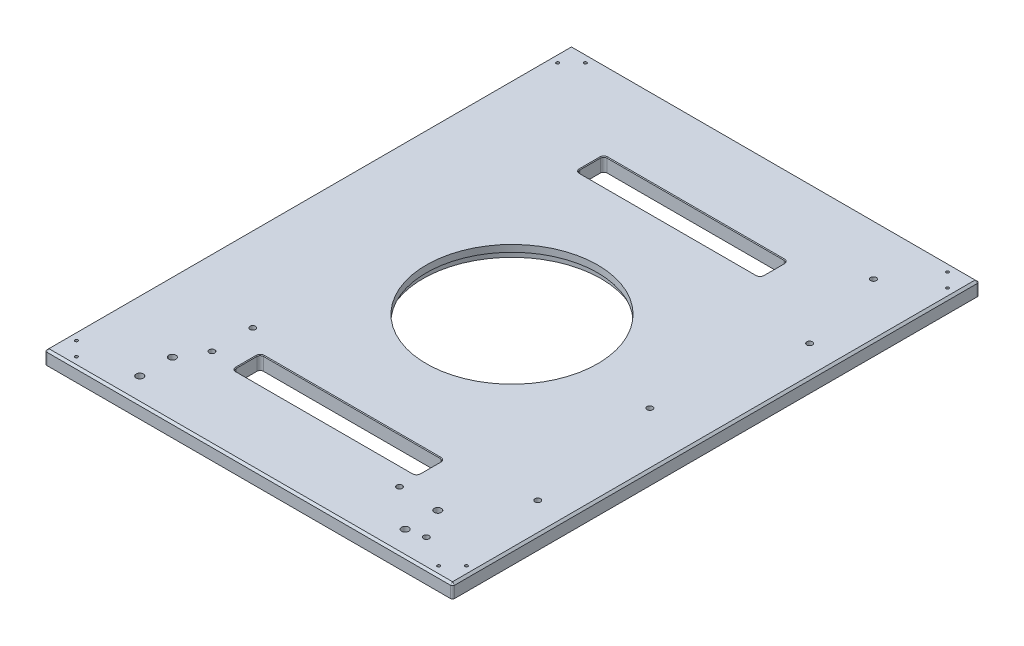
SolidWorks part; units mm, degrees
material "6061-T6 (SS)"
ref_plane "Front Plane" through (0, 0, 0) normal (0, 0, 1) x (1, 0, 0)
ref_plane "Top Plane" through (0, 0, 0) normal (0, 1, 0) x (1, 0, 0)
ref_plane "Right Plane" through (0, 0, 0) normal (1, 0, 0) x (0, 0, -1)
sketch "Sketch1" plane through (0, 0, 0) normal (0, 1, 0) x (1, 0, 0)
  line L1 (-300, -387.5) -> (300, -387.5)
  line L2 (-300, -387.5) -> (-300, 387.5)
  line L3 (-300, 387.5) -> (300, 387.5)
  line L4 (300, -387.5) -> (300, 387.5)
  line L5 (-300, -387.5) -> (300, 387.5) construction
  line L6 (-300, 387.5) -> (300, -387.5) construction
  point P0 (0, 0)
  dimension "D1" = 775
  dimension "D2" = 600
extrude "MainPlate" add sketch "Sketch1" against normal blind 20
sketch "Sketch2" plane through (0, -20, 0) normal (0, -1, 0) x (-1, 0, 0)
  circle A0 centre (0, 0) radius 126
  dimension "D1" = 252
extrude "BuildPlate" cut sketch "Sketch2" against normal through all
sketch "Sketch3" plane through (0, -20, 0) normal (0, 1, 0) x (-1, 0, 0)
  circle A0 centre (0, 0) radius 131
  dimension "D1" = 262
extrude "BuildCylinderRelief" cut sketch "Sketch3" along normal blind 10
hole_wizard "Z-axisHelicoils" positions "Sketch4" profile "Sketch5" tap size "M8x1.25" standard "Helicoil® Metric"
sketch "Sketch4" plane through (0, -20, 0) normal (0, 1, 0) x (1, 0, 0)
  line L0 (0, 0) -> (148.5, 0) construction
  circle A0 centre (0, 0) radius 148.5 construction
  point P0 (148.5, 0)
  dimension "D1" = 297
cosmetic thread "Hole Thread1" parameters "D1"=14.19, "D2"=9.787
sketch "Sketch5" plane through (148.5, -20, 0) normal (1, 0, 0) x (0, 0, -1)
  line L0 (0, 0) -> (0, 19.6436)
  line L1 (0, 19.6436) -> (4.15, 17.15)
  line L2 (4.15, 17.15) -> (4.15, 0)
  line L5 (4.15, 0) -> (0, 0)
  line L10 (0, 19.6436) -> (-4.15, 17.15) construction
  line L11 (0, -6.35) -> (0, 107.95) construction
  dimension "Tap Drill Dia." = 8.3
  dimension "Tap Drill Depth" = 17.15
  dimension "Drill Angle" = 118
pattern_circular "Z-axisMountHoles" count 6 over 360 about axis through (0, -10, 0) along (0, -1, 0) of "Z-axisHelicoils"
cosmetic thread "Hole Thread2" parameters "D1"=14.19, "D2"=9.787
cosmetic thread "Hole Thread3" parameters "D1"=14.19, "D2"=9.787
cosmetic thread "Hole Thread4" parameters "D1"=14.19, "D2"=9.787
cosmetic thread "Hole Thread5" parameters "D1"=14.19, "D2"=9.787
cosmetic thread "Hole Thread6" parameters "D1"=14.19, "D2"=9.787
sketch "Sketch6" plane through (0, -20, 0) normal (0, -1, 0) x (-1, 0, 0)
  line L0 (0, 0) -> (0, 250) construction
  line L1 (130, 230) -> (-130, 230)
  line L2 (135, 235) -> (135, 265)
  line L3 (130, 270) -> (-130, 270)
  line L4 (-135, 235) -> (-135, 265)
  line L5 (135, 230) -> (-135, 270) construction
  line L6 (135, 270) -> (-135, 230) construction
  arc A0 (135, 265) -> (130, 270) centre (130, 265) ccw
  arc A1 (130, 230) -> (135, 235) centre (130, 235) ccw
  arc A2 (-130, 230) -> (-135, 235) centre (-130, 235) cw
  arc A3 (-130, 270) -> (-135, 265) centre (-130, 265) ccw
  point P0 (0, 250)
  dimension "D4" = 5
  dimension "D1" = 230
  dimension "D2" = 40
  dimension "D3" = 270
extrude "Overflow" cut sketch "Sketch6" against normal through all
hole_wizard "M5 Tapped Hole1" positions "Sketch7" profile "Sketch8" tap size "M5" standard "ISO"
sketch "Sketch7" plane through (0, -20, 0) normal (0, 1, 0) x (1, 0, 0)
  line L0 (130, 230) -> (-130, 230) construction
  line L1 (0, 217) -> (0, 0) construction
  line L3 (135, 250) -> (-135, 250) construction
  line L4 (135, 265) -> (135, 235) construction
  line L5 (-135, 235) -> (-135, 265) construction
  line L7 (148, 250) -> (135, 250) construction
  line L9 (0, 217) -> (60, 217) construction
  line L10 (60, 217) -> (120, 217) construction
  line L12 (148, 217) -> (148, 250) construction
  line L15 (148, 217) -> (120, 217) construction
  point P0 (0, 217)
  point P8 (120, 217)
  point P10 (60, 217)
  point P12 (148, 250)
  point P38 (148, 217)
  dimension "D1" = 13
  dimension "D2" = 13
  dimension "D3" = 60
sketch "Sketch8" plane through (0, -20, -217) normal (1, 0, 0) x (0, 0, -1)
  line L0 (0, 0) -> (0, 13.6618)
  line L1 (0, 13.6618) -> (2.1, 12.4)
  line L2 (2.1, 12.4) -> (2.1, 0)
  line L5 (2.1, 0) -> (0, 0)
  line L10 (0, 13.6618) -> (-2.1, 12.4) construction
  line L11 (0, -6.35) -> (0, 107.95) construction
  dimension "Tap Drill Dia." = 4.2
  dimension "Tap Drill Depth" = 12.4
  dimension "Drill Angle" = 118
cosmetic thread "Hole Thread7" parameters "D1"=10, "D2"=5
cosmetic thread "Hole Thread32" parameters "D1"=10, "D2"=5
cosmetic thread "Hole Thread33" parameters "D1"=10, "D2"=5
cosmetic thread "Hole Thread34" parameters "D1"=10, "D2"=5
cosmetic thread "Hole Thread96" parameters "D1"=10, "D2"=5
mirror "Mirror3" about plane through (0, 0, 0) normal (1, 0, 0) of "M5 Tapped Hole1"
cosmetic thread "Hole Thread35" parameters "D1"=10, "D2"=5
cosmetic thread "Hole Thread36" parameters "D1"=10, "D2"=5
cosmetic thread "Hole Thread37" parameters "D1"=10, "D2"=5
cosmetic thread "Hole Thread97" parameters "D1"=10, "D2"=5
ref_plane "Plane1" through (0, 0, -250) normal (0, 0, 1) x (1, 0, 0)
mirror "Mirror4" about plane through (0, 0, -250) normal (0, 0, 1) of "Mirror3"
cosmetic thread "Hole Thread39" parameters "D1"=10, "D2"=5
cosmetic thread "Hole Thread40" parameters "D1"=10, "D2"=5
cosmetic thread "Hole Thread42" parameters "D1"=10, "D2"=5
cosmetic thread "Hole Thread44" parameters "D1"=10, "D2"=5
cosmetic thread "Hole Thread98" parameters "D1"=10, "D2"=5
cosmetic thread "Hole Thread99" parameters "D1"=10, "D2"=5
sketch "Sketch9" plane through (0, 0, 0) normal (0, 1, 0) x (-1, 0, 0)
  line L4 (-130, -270) -> (130, -270)
  line L5 (-135, -235) -> (-135, -265)
  line L6 (130, -230) -> (-130, -230)
  line L7 (135, -265) -> (135, -235)
  line L8 (-130, -270) -> (130, -270) construction
  line L9 (-135, -235) -> (-135, -265) construction
  line L10 (130, -230) -> (-130, -230) construction
  line L11 (135, -265) -> (135, -235) construction
  arc A4 (130, -270) -> (135, -265) centre (130, -265) ccw
  arc A5 (-135, -265) -> (-130, -270) centre (-130, -265) ccw
  arc A6 (-130, -230) -> (-135, -235) centre (-130, -235) ccw
  arc A7 (135, -235) -> (130, -230) centre (130, -235) ccw
  arc A8 (130, -270) -> (135, -265) centre (130, -265) ccw construction
  arc A9 (-135, -265) -> (-130, -270) centre (-130, -265) ccw construction
  arc A10 (-130, -230) -> (-135, -235) centre (-130, -235) ccw construction
  arc A11 (135, -235) -> (130, -230) centre (130, -235) ccw construction
  spline S0 degree 3 poles (135, -263.0491) (135, -254.3497) (135, -245.6503) (135, -236.9509) (135, -236.7341) (135, -236.3006) (135, -235.6503) (135, -235.2168) (135, -235) (135, -234.7832) (135, -234.3497) (134.8422, -233.6982) (134.7024, -233.2868) (134.6194, -233.0866) (134.1051, -231.8451) (133.1549, -230.8949) (131.9134, -230.3806) (131.7132, -230.2976) (131.3018, -230.1578) (130.6503, -230) (130.2168, -230) (130, -230) (129.7832, -230) (129.3497, -230) (128.6994, -230) (128.2659, -230) (128.0491, -230) (42.683, -230) (-42.683, -230) (-128.0491, -230) (-128.2659, -230) (-128.6994, -230) (-129.3497, -230) (-129.7832, -230) (-130, -230) (-130.2168, -230) (-130.6503, -230) (-131.3018, -230.1578) (-131.7132, -230.2976) (-131.9134, -230.3806) (-133.1549, -230.8949) (-134.1051, -231.8451) (-134.6194, -233.0866) (-134.7024, -233.2868) (-134.8422, -233.6982) (-135, -234.3497) (-135, -234.7832) (-135, -235) (-135, -235.2168) (-135, -235.6503) (-135, -236.3006) (-135, -236.7341) (-135, -236.9509) (-135, -245.6503) (-135, -254.3497) (-135, -263.0491) (-135, -263.2659) (-135, -263.6994) (-135, -264.3497) (-135, -264.7832) (-135, -265) (-135, -265.2168) (-135, -265.6503) (-134.8422, -266.3018) (-134.7024, -266.7132) (-134.6194, -266.9134) (-134.1051, -268.1549) (-133.1549, -269.1051) (-131.9134, -269.6194) (-131.7132, -269.7024) (-131.3018, -269.8422) (-130.6503, -270) (-130.2168, -270) (-130, -270) (-129.7832, -270) (-129.3497, -270) (-128.6994, -270) (-128.2659, -270) (-128.0491, -270) (-42.683, -270) (42.683, -270) (128.0491, -270) (128.2659, -270) (128.6994, -270) (129.3497, -270) (129.7832, -270) (130, -270) (130.2168, -270) (130.6503, -270) (131.3018, -269.8422) (131.7132, -269.7024) (131.9134, -269.6194) (133.1549, -269.1051) (134.1051, -268.1549) (134.6194, -266.9134) (134.7024, -266.7132) (134.8422, -266.3018) (135, -265.6503) (135, -265.2168) (135, -265) (135, -264.7832) (135, -264.3497) (135, -263.6994) (135, -263.2659) (135, -263.0491) (135, -254.3497) (135, -245.6503) knots -0.001064 0 0 0 0.04272 0.04272 0.04272 0.043784 0.044849 0.045913 0.045913 0.045913 0.046978 0.048042 0.049107 0.049107 0.049107 0.055371 0.055371 0.055371 0.056435 0.0575 0.058564 0.058564 0.058564 0.059629 0.060693 0.061758 0.061758 0.061758 0.480962 0.480962 0.480962 0.482027 0.483091 0.484156 0.484156 0.484156 0.48522 0.486285 0.487349 0.487349 0.487349 0.493613 0.493613 0.493613 0.494678 0.495742 0.496807 0.496807 0.496807 0.497871 0.498936 0.5 0.5 0.5 0.54272 0.54272 0.54272 0.543784 0.544849 0.545913 0.545913 0.545913 0.546978 0.548042 0.549107 0.549107 0.549107 0.555371 0.555371 0.555371 0.556435 0.5575 0.558564 0.558564 0.558564 0.559629 0.560693 0.561758 0.561758 0.561758 0.980962 0.980962 0.980962 0.982027 0.983091 0.984156 0.984156 0.984156 0.98522 0.986285 0.987349 0.987349 0.987349 0.993613 0.993613 0.993613 0.994678 0.995742 0.996807 0.996807 0.996807 0.997871 0.998936 1 1 1 1.04272 1.04272 1.04272 weights 1 1 1 1 1 1 1 1 1 1 1 1 1 1 0.949253 0.949253 1 1 1 1 1 1 1 1 1 1 1 1 1 1 1 1 1 1 1 1 1 1 1 1 0.949253 0.949253 1 1 1 1 1 1 1 1 1 1 1 1 1 1 1 1 1 1 1 1 1 1 1 1 0.949253 0.949253 1 1 1 1 1 1 1 1 1 1 1 1 1 1 1 1 1 1 1 1 1 1 1 1 0.949253 0.949253 1 1 1 1 1 1 1 1 1 1 1 1 1 only from (135, -263.0491) to (135, -263.0491)
  dimension "D1" = 0
sketch "Sketch10" plane through (0, 0, 0) normal (0, 1, 0) x (1, 0, 0)
  line L0 (0, 0) -> (0, -255.5) construction
  line L1 (-130, -275.5) -> (130, -275.5)
  line L2 (-135, -270.5) -> (-135, -240.5)
  line L3 (-130, -235.5) -> (130, -235.5)
  line L4 (135, -270.5) -> (135, -240.5)
  line L5 (-135, -275.5) -> (135, -235.5) construction
  line L6 (-135, -235.5) -> (135, -275.5) construction
  line L7 (-300, -387.5) -> (300, -387.5) construction
  line L8 (0, 230) -> (0, 270) construction
  line L9 (-130, 230) -> (130, 230) construction
  line L10 (-130, 270) -> (130, 270) construction
  line L11 (0, -275.5) -> (0, -235.5) construction
  arc A0 (130, -275.5) -> (135, -270.5) centre (130, -270.5) ccw
  arc A1 (130, -235.5) -> (135, -240.5) centre (130, -240.5) cw
  arc A2 (-130, -275.5) -> (-135, -270.5) centre (-130, -270.5) cw
  arc A3 (-135, -240.5) -> (-130, -235.5) centre (-130, -240.5) cw
  point P0 (0, -255.5)
  dimension "D4" = 5
  dimension "D1" = 270
  dimension "D3" = 132
extrude "Cut-Extrude1" cut sketch "Sketch10" against normal through all
sketch "Sketch11" plane through (0, 0, 0) normal (0, 1, 0) x (1, 0, 0)
  line L1 (300, 387.5) -> (280, 387.5) construction
  line L2 (300, 387.5) -> (300, 367.5) construction
  line L3 (300, 367.5) -> (280, 367.5) construction
  line L4 (280, 387.5) -> (280, 367.5) construction
  dimension "D1" = 20
sketch "Sketch12" plane through (0, -20, 0) normal (0, -1, 0) x (-1, 0, 0)
  line L0 (-300, -387.5) -> (-300, 387.5) construction
  line L1 (-240, -327.5) -> (240, -327.5) construction
  line L2 (-240, -327.5) -> (-240, 327.5) construction
  line L3 (-240, 327.5) -> (240, 327.5) construction
  line L4 (240, -327.5) -> (240, 327.5) construction
  line L5 (300, -387.5) -> (-300, -387.5) construction
  line L6 (0, 0) -> (0, -327.5) construction
  line L7 (-240, 0) -> (0, 0) construction
  dimension "D1" = 60
  dimension "D2" = 60
hole_wizard "M8 Tapped Hole1" positions "Sketch13" profile "Sketch14" tap size "M8" standard "ISO"
sketch "Sketch13" plane through (0, -20, 0) normal (0, -1, 0) x (-1, 0, 0)
  line L0 (-240, -327.5) -> (-240, 327.5) construction
  line L1 (-240, 327.5) -> (240, 327.5) construction
  line L2 (-240, 0) -> (0, 0) construction
  line L3 (0, 0) -> (0, -327.5) construction
  line L4 (0, 0) -> (0, -327.5) construction
  line L5 (-240, 0) -> (0, 0) construction
  point P0 (-240, 150)
  point P4 (-110, 327.5)
  point P14 (-240, -150)
  point P15 (-110, -327.5)
  point P16 (110, -327.5)
  point P17 (240, -150)
  point P18 (240, 150)
  point P19 (110, 327.5)
  dimension "D1" = 150
  dimension "D2" = 130
sketch "Sketch14" plane through (240, -20, -150) normal (1, 0, 0) x (0, 0, -1)
  line L0 (0, 0) -> (0, 15)
  line L1 (0, 15) -> (3.4, 12.9571)
  line L2 (3.4, 12.9571) -> (3.4, 0)
  line L5 (3.4, 0) -> (0, 0)
  line L10 (0, 15) -> (-3.4, 12.9571) construction
  line L11 (0, -6.35) -> (0, 107.95) construction
  dimension "Tap Drill Dia." = 6.8
  dimension "Tap Drill Depth" = 15
  dimension "Drill Angle" = 118
cosmetic thread "Hole Thread15" parameters "D1"=12, "D2"=8
cosmetic thread "Hole Thread16" parameters "D1"=12, "D2"=8
cosmetic thread "Hole Thread17" parameters "D1"=12, "D2"=8
cosmetic thread "Hole Thread18" parameters "D1"=12, "D2"=8
cosmetic thread "Hole Thread19" parameters "D1"=12, "D2"=8
cosmetic thread "Hole Thread20" parameters "D1"=12, "D2"=8
cosmetic thread "Hole Thread21" parameters "D1"=12, "D2"=8
cosmetic thread "Hole Thread22" parameters "D1"=12, "D2"=8
hole_wizard "M5 Tapped Hole2" positions "Sketch15" profile "Sketch16" tap size "M5" standard "ISO"
sketch "Sketch15" plane through (0, 0, 0) normal (0, 1, 0) x (1, 0, 0)
  line L0 (300, 387.5) -> (-300, 387.5) construction
  line L1 (300, -387.5) -> (300, 387.5) construction
  point P0 (266.5, 374.5)
  point P2 (287, 354)
  dimension "D1" = 13
  dimension "D2" = 33.5
  dimension "D3" = 13
  dimension "D4" = 33.5
sketch "Sketch16" plane through (266.5, 0, -374.5) normal (1, 0, 0) x (0, 0, 1)
  line L0 (0, 0) -> (0, 12.4)
  line L1 (0, 12.4) -> (2.1, 11.1382)
  line L2 (2.1, 11.1382) -> (2.1, 0)
  line L5 (2.1, 0) -> (0, 0)
  line L10 (0, 12.4) -> (-2.1, 11.1382) construction
  line L11 (0, -6.35) -> (0, 107.95) construction
  dimension "Tap Drill Dia." = 4.2
  dimension "Tap Drill Depth" = 12.4
  dimension "Drill Angle" = 118
cosmetic thread "Hole Thread23" parameters "D1"=10, "D2"=5
cosmetic thread "Hole Thread24" parameters "D1"=10, "D2"=5
mirror "Mirror1" about plane through (0, 0, 0) normal (1, 0, 0) of "M5 Tapped Hole2"
cosmetic thread "Hole Thread25" parameters "D1"=10, "D2"=5
cosmetic thread "Hole Thread26" parameters "D1"=10, "D2"=5
mirror "Mirror2" about plane through (0, 0, 0) normal (0, 0, 1) of "Mirror1"
cosmetic thread "Hole Thread27" parameters "D1"=10, "D2"=5
cosmetic thread "Hole Thread28" parameters "D1"=10, "D2"=5
cosmetic thread "Hole Thread29" parameters "D1"=10, "D2"=5
cosmetic thread "Hole Thread30" parameters "D1"=10, "D2"=5
chamfer "Chamfer1" distance 1 angle 45 16 edges at (0, 0, -270) (133.5355, 0, -268.5355) (-133.5355, 0, -268.5355) (135, 0, -250) (-135, 0, -250) (133.5355, 0, -231.4645) (-133.5355, 0, -231.4645) (0, 0, -230) (133.5355, 0, 274.0355) (135, 0, 255.5) (133.5355, 0, 236.9645) (0, 0, 235.5) (-133.5355, 0, 236.9645) (-135, 0, 255.5) (-133.5355, 0, 274.0355) (0, 0, 275.5)
fillet "Fillet1" radius 3 4 edges at (-300, -10, -387.5) (-300, -10, 387.5) (300, -10, 387.5) (300, -10, -387.5)
chamfer "Chamfer2" distance 3 angle 45 8 edges at (0, 0, 387.5) (-300, 0, 0) (0, 0, -387.5) (300, 0, 0) (299.1213, 0, -386.6213) (299.1213, 0, 386.6213) (-299.1213, 0, 386.6213) (-299.1213, 0, -386.6213)
pattern_linear "LPattern1" count 2 spacing 505.5 along (0, 0, 1) of "Mirror4", "Mirror3", "M5 Tapped Hole1"
cosmetic thread "Hole Thread45" parameters "D1"=10, "D2"=5
cosmetic thread "Hole Thread46" parameters "D1"=10, "D2"=5
cosmetic thread "Hole Thread47" parameters "D1"=10, "D2"=5
cosmetic thread "Hole Thread48" parameters "D1"=10, "D2"=5
cosmetic thread "Hole Thread49" parameters "D1"=10, "D2"=5
cosmetic thread "Hole Thread50" parameters "D1"=10, "D2"=5
cosmetic thread "Hole Thread51" parameters "D1"=10, "D2"=5
cosmetic thread "Hole Thread52" parameters "D1"=10, "D2"=5
cosmetic thread "Hole Thread53" parameters "D1"=10, "D2"=5
cosmetic thread "Hole Thread54" parameters "D1"=10, "D2"=5
cosmetic thread "Hole Thread55" parameters "D1"=10, "D2"=5
cosmetic thread "Hole Thread100" parameters "D1"=10, "D2"=5
cosmetic thread "Hole Thread101" parameters "D1"=10, "D2"=5
cosmetic thread "Hole Thread102" parameters "D1"=10, "D2"=5
cosmetic thread "Hole Thread103" parameters "D1"=10, "D2"=5
hole_wizard "Tapped Hole for M8x1.25 Helicoil1" positions "Sketch19" profile "Sketch20" tap size "M8x1.25" standard "Helicoil® Metric"
sketch "Sketch19" plane through (0, 0, 0) normal (0, 1, 0) x (1, 0, 0)
  point P0 (221, 310.9)
  point P3 (256, 181.9)
  point P6 (221, -18.1)
  point P9 (256, -218.1)
  point P12 (221, -347.1)
sketch "Sketch20" plane through (221, 0, -310.9) normal (1, 0, 0) x (0, 0, 1)
  line L0 (0, 0) -> (0, 13)
  line L1 (0, 13) -> (4.15, 10.5064)
  line L2 (4.15, 10.5064) -> (4.15, 0)
  line L5 (4.15, 0) -> (0, 0)
  line L10 (0, 13) -> (-4.15, 10.5064) construction
  line L11 (0, -6.35) -> (0, 107.95) construction
  dimension "Tap Drill Dia." = 8.3
  dimension "Tap Drill Depth" = 13
  dimension "Drill Angle" = 118
cosmetic thread "Hole Thread80" parameters "D1"=9.3, "D2"=9.787
cosmetic thread "Hole Thread81" parameters "D1"=9.3, "D2"=9.787
cosmetic thread "Hole Thread82" parameters "D1"=9.3, "D2"=9.787
cosmetic thread "Hole Thread83" parameters "D1"=9.3, "D2"=9.787
cosmetic thread "Hole Thread84" parameters "D1"=9.3, "D2"=9.787
hole_wizard "Tapped Hole for M10x1.5 Helicoil1" positions "Sketch21" profile "Sketch22" tap size "M10x1.5" standard "Helicoil® Metric"
sketch "Sketch21" plane through (0, 0, 0) normal (0, 1, 0) x (1, 0, 0)
  point P0 (-195.25, -304.5)
  point P3 (-195.25, -352.5)
  point P6 (195.25, -304.5)
  point P9 (195.25, -352.5)
sketch "Sketch22" plane through (-195.25, 0, 304.5) normal (1, 0, 0) x (0, 0, 1)
  line L0 (0, 0) -> (0, 19)
  line L1 (0, 19) -> (5.25, 15.8455)
  line L2 (5.25, 15.8455) -> (5.25, 0)
  line L5 (5.25, 0) -> (0, 0)
  line L10 (0, 19) -> (-5.25, 15.8455) construction
  line L11 (0, -6.35) -> (0, 107.95) construction
  dimension "Tap Drill Dia." = 10.5
  dimension "Tap Drill Depth" = 19
  dimension "Drill Angle" = 118
cosmetic thread "Hole Thread89" parameters "D1"=11.5, "D2"=12.131
cosmetic thread "Hole Thread91" parameters "D1"=11.5, "D2"=12.131
cosmetic thread "Hole Thread104" parameters "D1"=11.5, "D2"=12.131
cosmetic thread "Hole Thread105" parameters "D1"=11.5, "D2"=12.131
hole_wizard "Tapped Hole for M8x1.25 Helicoil2" positions "Sketch23" profile "Sketch24" tap size "M8x1.25" standard "Helicoil® Metric"
sketch "Sketch23" plane through (0, 0, 0) normal (0, 1, 0) x (1, 0, 0)
  point P0 (-173.5, -208)
  point P3 (-173.5, -268)
  point P6 (137, -302.5)
sketch "Sketch24" plane through (-173.5, 0, 208) normal (1, 0, 0) x (0, 0, 1)
  line L0 (0, 0) -> (0, 19.5)
  line L1 (0, 19.5) -> (4.15, 17.0064)
  line L2 (4.15, 17.0064) -> (4.15, 0)
  line L5 (4.15, 0) -> (0, 0)
  line L10 (0, 19.5) -> (-4.15, 17.0064) construction
  line L11 (0, -6.35) -> (0, 107.95) construction
  dimension "Tap Drill Dia." = 8.3
  dimension "Tap Drill Depth" = 19.5
  dimension "Drill Angle" = 118
cosmetic thread "Hole Thread93" parameters "D1"=9.3, "D2"=9.787
cosmetic thread "Hole Thread94" parameters "D1"=9.3, "D2"=9.787
cosmetic thread "Hole Thread95" parameters "D1"=9.3, "D2"=9.787
equation "\"D1@Sketch7\"=\"D2@Sketch7\""
